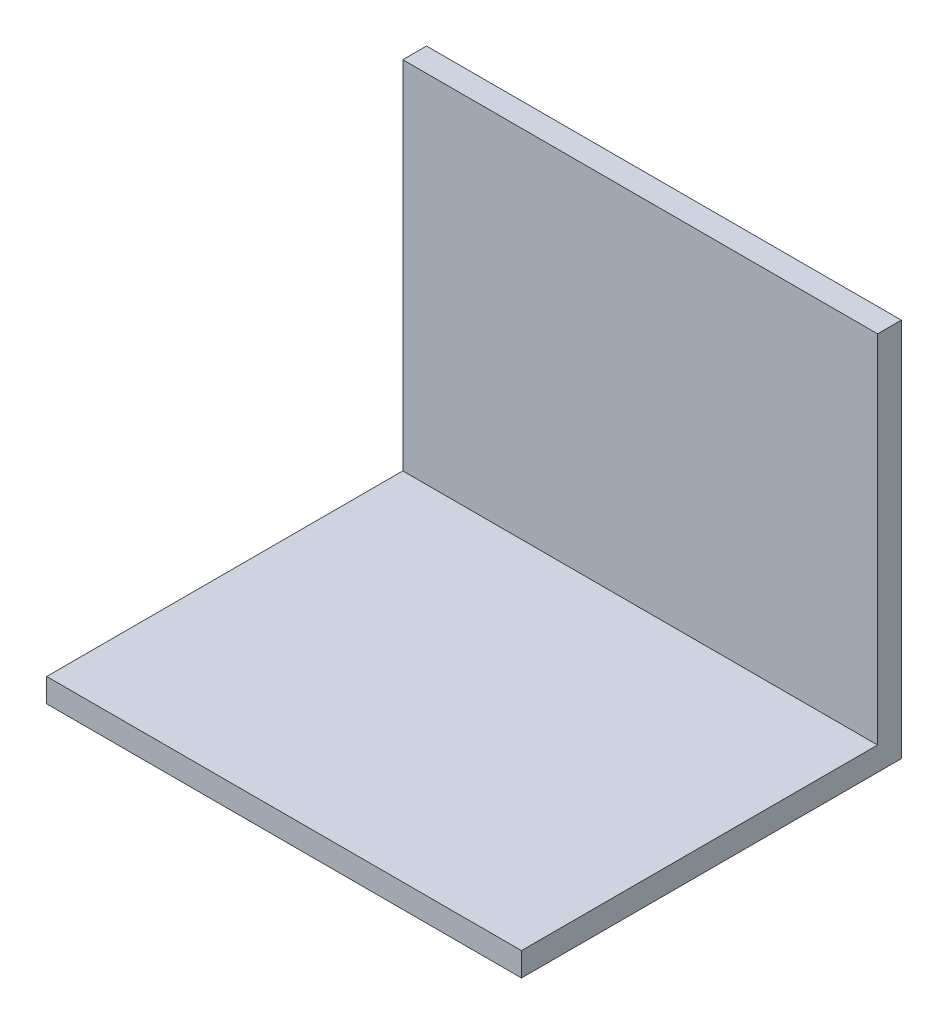
SolidWorks part; units mm, degrees
ref_plane "Front Plane" through (0, 0, 0) normal (0, 0, 1) x (1, 0, 0)
ref_plane "Top Plane" through (0, 0, 0) normal (0, 1, 0) x (1, 0, 0)
ref_plane "Right Plane" through (0, 0, 0) normal (1, 0, 0) x (0, 0, -1)
sketch "Sketch1" plane through (0, 0, 0) normal (1, 0, 0) x (0, 0, -1)
  line L1 (-3.175, 0) -> (-50.8, 0)
  line L2 (0, 0) -> (0, -3.175)
  line L3 (0, -3.175) -> (-50.8, -3.175)
  line L4 (-50.8, 0) -> (-50.8, -3.175)
  line L6 (0, 0) -> (0, 47.625)
  line L7 (0, 47.625) -> (-3.175, 47.625)
  line L8 (-3.175, 0) -> (-3.175, 47.625)
  dimension "D1" = 3.175
  dimension "D2" = 50.8
  dimension "D3" = 50.8
  dimension "D4" = 3.175
extrude "Boss-Extrude1" add sketch "Sketch1" along normal blind 63.5
